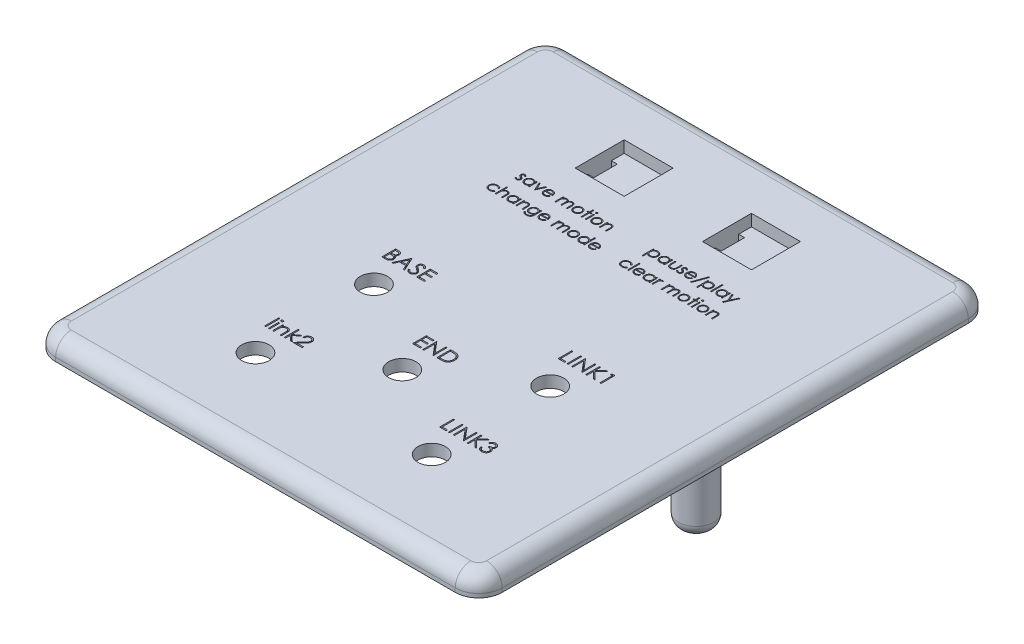
SolidWorks part; units mm, degrees
ref_plane "Front Plane" through (0, 0, 0) normal (0, 0, 1) x (1, 0, 0)
ref_plane "Top Plane" through (0, 0, 0) normal (0, 1, 0) x (1, 0, 0)
ref_plane "Right Plane" through (0, 0, 0) normal (1, 0, 0) x (0, 0, -1)
sketch "Sketch1" plane through (0, 0, 0) normal (0, 1, 0) x (1, 0, 0)
  line L1 (-57, -65.5) -> (57, -65.5)
  line L2 (-57, -65.5) -> (-57, 65.5)
  line L3 (-57, 65.5) -> (57, 65.5)
  line L4 (57, -65.5) -> (57, 65.5)
  line L5 (-57, -65.5) -> (57, 65.5) construction
  line L6 (-57, 65.5) -> (57, -65.5) construction
  point P0 (0, 0)
  point P6 (57, 4.5)
  point P7 (57, -0.5)
  point P8 (2466.975, 212.5266)
  point P9 (57, -25.5)
  point P10 (57, -984.6473)
  point P11 (57, -1284.6848)
  point P12 (57, -1468.0411)
  point P13 (52, 65.5)
  point P14 (-52, 65.5)
  point P15 (-42, 65.5)
  point P16 (42, 65.5)
  point P17 (57, -55.5)
  point P18 (57, -65.5)
  point P21 (57, 60.5)
  point P22 (57, -30.5)
  dimension "D1" = 84
  dimension "D2" = 5
  dimension "D3" = 5
  dimension "D4" = 10
  dimension "D5" = 10
  dimension "D7" = 5
  dimension "D8" = 25
  dimension "D9" = 5
  dimension "D10" = 25
  dimension "D11" = 10
  dimension "D12" = 10
  dimension "D6" = 5
  dimension "D13" = 56
extrude "Boss-Extrude1" add sketch "Sketch1" along normal blind 5
sketch "Sketch3" plane through (0, 0, 0) normal (0, -1, 0) x (1, 0, 0)
  line L0 (52, -60.5) -> (52, 60.5)
  line L1 (52, 60.5) -> (-52, 60.5)
  line L2 (-52, 60.5) -> (-52, -60.5)
  line L3 (-52, -60.5) -> (52, -60.5)
  line L4 (57, -65.5) -> (57, 65.5)
  line L5 (57, 65.5) -> (-57, 65.5)
  line L6 (-57, 65.5) -> (-57, -65.5)
  line L7 (-57, -65.5) -> (57, -65.5)
  line L8 (57, -65.5) -> (57, 65.5)
  line L9 (57, 65.5) -> (-57, 65.5)
  line L10 (-57, 65.5) -> (-57, -65.5)
  line L11 (-57, -65.5) -> (57, -65.5)
  dimension "D1" = 0
  dimension "D2" = 5
extrude "Cut-Extrude2" cut sketch "Sketch3" against normal offset from surface (2 mm away) 3 contours L0 L1 L2 L3 up to face at (0, 5, 0)
fillet "Fillet1" radius 6 4 edges at (-57, 2.5, 65.5) (-57, 2.5, -65.5) (57, 2.5, -65.5) (57, 2.5, 65.5)
fillet "Fillet2" radius 4 8 edges at (-55.2426, 5, -63.7426) (0, 5, -65.5) (55.2426, 5, -63.7426) (57, 5, 0) (55.2426, 5, 63.7426) (0, 5, 65.5) (-55.2426, 5, 63.7426) (-57, 5, 0)
fillet "Fillet3" radius 6 4 edges at (-52, 1, 60.5) (-52, 1, -60.5) (52, 1, 60.5) (52, 1, -60.5)
sketch "Sketch5" plane through (0, 0, 0) normal (0, -1, 0) x (1, 0, 0)
  line L0 (-52, 0) -> (-57, 0) construction
  line L1 (-52, -54.5) -> (-52, 54.5) construction
  line L2 (-57, -59.5) -> (-57, 59.5) construction
  line L3 (0, -13.75) -> (0, 13.75) construction
  line L4 (52, 0) -> (57, 0) construction
  circle A0 centre (-47, 0) radius 7.5
  circle A1 centre (47, 0) radius 7.5
  point P8 (-54.5, 0)
  point P10 (-54.5, 0)
  point P12 (-47, 0)
  point P17 (47, 0)
  point P18 (54.5, 0)
  dimension "D1" = 15
extrude "Boss-Extrude2" add sketch "Sketch5" against normal up to surface (2 mm away) up to face at (0, 2, 0)
fillet "Fillet4" radius 6 2 edges at (-52, 1, 5.5902) (-52, 1, -5.5902)
fillet "Fillet7" radius 6 2 edges at (52, 1, 5.5902) (52, 1, -5.5902)
sketch "Sketch15" plane through (0, 0, 0) normal (0, -1, 0) x (1, 0, 0)
  circle A0 centre (-47, 0) radius 4.5
  circle A1 centre (47, 0) radius 4.5
  dimension "D1" = 9
  dimension "D2" = 9
extrude "Boss-Extrude4" add sketch "Sketch15" along normal blind 20
fillet "Fillet8" radius 3 2 edges at (47, -20, -4.5) (-47, -20, -4.5)
sketch "Sketch10" plane through (0, 0, 0) normal (0, 1, 0) x (1, 0, 0)
  line L4 (53, -59.5) -> (53, 59.5)
  line L5 (-51, -61.5) -> (51, -61.5)
  line L6 (-53, 59.5) -> (-53, -59.5)
  line L7 (51, 61.5) -> (-51, 61.5)
  line L8 (53, -59.5) -> (53, 59.5)
  line L9 (-51, -61.5) -> (51, -61.5)
  line L10 (-53, 59.5) -> (-53, -59.5)
  line L11 (51, 61.5) -> (-51, 61.5)
  line L12 (0, -25.5) -> (0, -30.5) construction
  circle A1 centre (-22.5, -43) radius 3.5
  circle A2 centre (-22.5, -43) radius 3.5
  circle A3 centre (22.5, -43) radius 3.5
  circle A4 centre (22.5, -43) radius 3.5
  circle A5 centre (22.5, -12.7493) radius 3.5
  circle A6 centre (22.5, -12.7493) radius 3.5
  circle A7 centre (-22.5, -12.7493) radius 3.5
  circle A8 centre (-22.5, -12.7493) radius 3.5
  arc A12 (51, -61.5) -> (53, -59.5) centre (51, -59.5) ccw
  arc A13 (-53, -59.5) -> (-51, -61.5) centre (-51, -59.5) ccw
  arc A14 (-51, 61.5) -> (-53, 59.5) centre (-51, 59.5) ccw
  arc A15 (53, 59.5) -> (51, 61.5) centre (51, 59.5) ccw
  arc A16 (51, -61.5) -> (53, -59.5) centre (51, -59.5) ccw
  arc A17 (-53, -59.5) -> (-51, -61.5) centre (-51, -59.5) ccw
  arc A18 (-51, 61.5) -> (-53, 59.5) centre (-51, 59.5) ccw
  arc A19 (53, 59.5) -> (51, 61.5) centre (51, 59.5) ccw
  circle A24 centre (0, -28) radius 3.5
  dimension "D1" = 0
  dimension "D2" = 0
  dimension "D3" = 0
  dimension "D4" = 0
  dimension "D5" = 0
extrude "Cut-Extrude3" cut sketch "Sketch10" along normal through all contours A6 | A4 | A2 | A8 | A24
sketch "Sketch11" plane through (0, 5, 0) normal (0, 1, 0) x (1, 0, 0)
  line L0 (0, 84.2173) -> (0, -80.3563) construction
  line L1 (-22.5, 51.1335) -> (-10, 38.6335) construction
  line L2 (-22.5, 51.1335) -> (-10, 51.1335)
  line L3 (-22.5, 51.1335) -> (-22.5, 38.6335)
  line L4 (-22.5, 38.6335) -> (-10, 38.6335)
  line L5 (-10, 51.1335) -> (-10, 38.6335)
  line L6 (-27.5, 33.6335) -> (-5, 33.6335)
  line L7 (-5, 56.1335) -> (-5, 33.6335)
  line L8 (-27.5, 56.1335) -> (-5, 56.1335)
  line L9 (-27.5, 56.1335) -> (-27.5, 33.6335)
  dimension "D1" = 12.5
  dimension "D2" = 12.5
  dimension "D3" = 10
  dimension "D4" = 5
extrude "Boss-Extrude3" add sketch "Sketch11" against normal blind 8 contours L8 L9 L6 L7 L2 L5 L4 L3 | L5 L2 L3 L4 region at (-16.25, 5, -44.8835) region at (-27.1818, 5, -44.8835)
sketch "Sketch13" plane through (0, 5, 0) normal (0, 1, 0) x (1, 0, 0)
  line L1 (-22.5, 51.1335) -> (-22.5, 38.6335) construction
  line L2 (-22.5, 51.1335) -> (-10, 51.1335) construction
  line L3 (-10, 51.1335) -> (-10, 38.6335) construction
  line L4 (-22.5, 38.6335) -> (-10, 38.6335) construction
  line L6 (-22.5, 51.1335) -> (-22.5, 38.6335)
  line L7 (-22.5, 51.1335) -> (-10, 51.1335)
  line L8 (-10, 51.1335) -> (-10, 38.6335)
  line L9 (-22.5, 38.6335) -> (-10, 38.6335)
extrude "Cut-Extrude5" cut sketch "Sketch13" against normal blind 3 and the other way through all
sketch "Sketch14" plane through (0, 2, 0) normal (0, 1, 0) x (1, 0, 0)
  line L0 (-27.5, 44.8835) -> (-5, 44.8835) construction
  line L1 (-27.5, 56.1335) -> (-27.5, 33.6335) construction
  line L2 (-5, 56.1335) -> (-5, 33.6335) construction
  line L3 (-22.5, 51.1335) -> (-22.5, 38.6335) construction
  line L4 (-22.5, 47.8835) -> (-21, 47.8835)
  line L5 (-22.5, 47.8835) -> (-22.5, 41.8835)
  line L6 (-22.5, 41.8835) -> (-21, 41.8835)
  line L7 (-21, 47.8835) -> (-21, 41.8835)
  line L8 (-16.25, 56.1335) -> (-16.25, 33.6335) construction
  line L9 (-27.5, 56.1335) -> (-5, 56.1335) construction
  line L10 (-27.5, 33.6335) -> (-5, 33.6335) construction
  line L11 (-10, 41.8835) -> (-11.5, 41.8835)
  line L12 (-11.5, 47.8835) -> (-11.5, 41.8835)
  line L13 (-10, 47.8835) -> (-11.5, 47.8835)
  line L14 (-10, 47.8835) -> (-10, 41.8835)
  point P12 (-22.5, 44.8835)
  dimension "D1" = 6
  dimension "D2" = 1.5
extrude "Cut-Extrude6" cut sketch "Sketch14" against normal through all both and the other way through all
fillet "Fillet10" radius 5 4 edges at (-16.25, 2, -33.6335) (-16.25, 2, -56.1335) (-5, 2, -44.8835) (-27.5, 2, -44.8835)
mirror "Mirror1" about plane through (0, 0, 0) normal (1, 0, 0) of "Fillet10", "Cut-Extrude6", "Cut-Extrude5", "Boss-Extrude3"
sketch "Sketch16" plane through (0, 2, 0) normal (0, -1, 0) x (1, 0, 0)
  line L3 (0, -84.2173) -> (0, 80.3563) construction
  line L4 (0, -84.2173) -> (0, 80.3563) construction
  line L8 (-11.8797, 0) -> (11.8797, 0)
  line B0 (-11.8797, 0) -> (-11.8797, -11.3723)
  line B1 (-11.8797, -11.3723) -> (-6.1936, -5.6862)
  line B2 (-6.1936, -5.6862) -> (0, -11.8797)
  line B3 (6.1936, -5.6862) -> (0, -11.8797)
  line B4 (11.8797, -11.3723) -> (6.1936, -5.6862)
  line B5 (11.8797, 0) -> (11.8797, -11.3723)
sketch_block_instance "Block1-1"
sketch_block "Block1"
extrude "Cut-Extrude7" cut sketch "Sketch16" against normal blind 1 contours L4 B3 B4 B5 L8 | B2 L4 L8 B0 B1 region at (-5.8529, 2, -4.5023) region at (5.8529, 2, -4.5023)
sketch "Sketch17" plane through (0, 5, 0) normal (0, 1, 0) x (1, 0, 0)
  line L0 (-30, 28.6335) -> (-2.5, 28.6335) construction
  line L1 (17, -5.6804) -> (28, -5.6804) construction
  line L2 (-22.5, 38.6335) -> (-10, 38.6335) construction
  line L3 (17, -5.6804) -> (28, -5.6804) construction
  line L4 (17, -35.9312) -> (28, -35.9312) construction
  line L5 (-27.5, 56.1335) -> (-27.5, 33.6335) construction
  line L6 (-5, 56.1335) -> (-5, 33.6335) construction
  line L7 (0, -13.75) -> (0, 13.75) construction
  line L8 (30, 28.6335) -> (2.5, 28.6335) construction
  line L9 (-28, -5.6804) -> (-17, -5.6804) construction
  line L10 (0, 84.2173) -> (0, -80.3563) construction
  line L11 (0, 84.2173) -> (0, -80.3563) construction
  line L12 (-48.8344, -28) -> (41.7036, -28) construction
  line L13 (17, -35.9312) -> (28, -35.9312) construction
  line L14 (17, -35.9312) -> (28, -35.9312) construction
  line L15 (-28, -35.9312) -> (-17, -35.9312) construction
  line L16 (-28, -35.9312) -> (-17, -35.9312) construction
  line L17 (-28, -35.9312) -> (-17, -35.9312) construction
  line L18 (-28, -35.9312) -> (-17, -35.9312) construction
  line L19 (-5.5, -20.9312) -> (5.5, -20.9312) construction
  line L20 (-5.5, -20.9312) -> (5.5, -20.9312) construction
  line L21 (-5.5, -20.9312) -> (5.5, -20.9312) construction
  line L22 (-5.5, -20.9312) -> (5.5, -20.9312) construction
  circle A0 centre (22.5, -12.7493) radius 3.5 construction
  circle A1 centre (22.5, -43) radius 3.5 construction
  circle A2 centre (0, -28) radius 3.5 construction
  circle A3 centre (-22.5, -43) radius 3.5 construction
  circle A4 centre (-22.5, -12.7493) radius 3.5 construction
  circle A5 centre (22.5, -12.7493) radius 3.5 construction
  circle A6 centre (22.5, -43) radius 3.5 construction
  circle A7 centre (0, -28) radius 3.5 construction
  circle A8 centre (-22.5, -43) radius 3.5 construction
  circle A9 centre (-22.5, -12.7493) radius 3.5 construction
  text T0 "save motion\r\nchange mode" font "Century Gothic" height in points 11
  text T1 "pause/play\r\nclear motion" font "Century Gothic" height in points 11
  text T2 "BASE"
  text T3 "LINK1"
  text T4 "LINK3"
  text T5 "link2"
  text T6 "END"
  point P20 (-26, -12.7493)
  point P31 (-19, -12.7493)
  point P32 (-26, -43)
  point P33 (-19, -43)
  point P34 (-3.5, -28)
  point P35 (3.5, -28)
  point P36 (19, -12.7493)
  point P37 (26, -12.7493)
  point P38 (19, -43)
  point P39 (26, -43)
  dimension "D1" = 10
  dimension "D2" = 2.5
  dimension "D3" = 2.5
  dimension "D4" = 2
  dimension "D5" = 2
extrude "Cut-Extrude9" cut sketch "Sketch17" against normal blind 2
equation "\"breadboard_width\"= 84"
equation "\"allowance1\"=5"
equation "\"base_thickness\"= 395.05"
equation "\"pot_length\"= 25"
equation "\"breadboard_length\"= 56"
equation "\"allowance2\"=10"
equation "\"base_thckness\"=5"
equation "\"breadboard_height\"= 9.5"
equation "\"allowance3\"=14.5"
equation "\"fillet1\"=6"
equation "\"screw_outer1\"= 15"
equation "\"battery_tray_height\"= 19.5"
equation "\"battery_tray_length\" =76"
equation "\"battery_tray_width\"=42"
equation "\"bms_width\"= 17.6"
equation "\"bms_height\"= 55"
equation "\"barrel_jack_height\"= 11.7"
equation "\"pot_pot\"=12"
equation "\"allowance4\" = 2"
equation "\"D1@Sketch1\"=\"breadboard_width\""
equation "\"D7@Sketch1\"=\"allowance1\""
equation "\"D9@Sketch1\"=\"allowance1\""
equation "\"D10@Sketch1\"=\"pot_length\""
equation "\"D12@Sketch1\"=\"allowance2\""
equation "\"D6@Sketch1\"=\"base_thckness\""
equation "\"D13@Sketch1\"=\"breadboard_length\""
equation "\"D1@Sketch5\"=\"screw_outer1\""
equation "\"screw\"=9"
equation "\"D2@Sketch15\"=\"screw\""
equation "\"D1@Sketch15\"=\"screw\""
